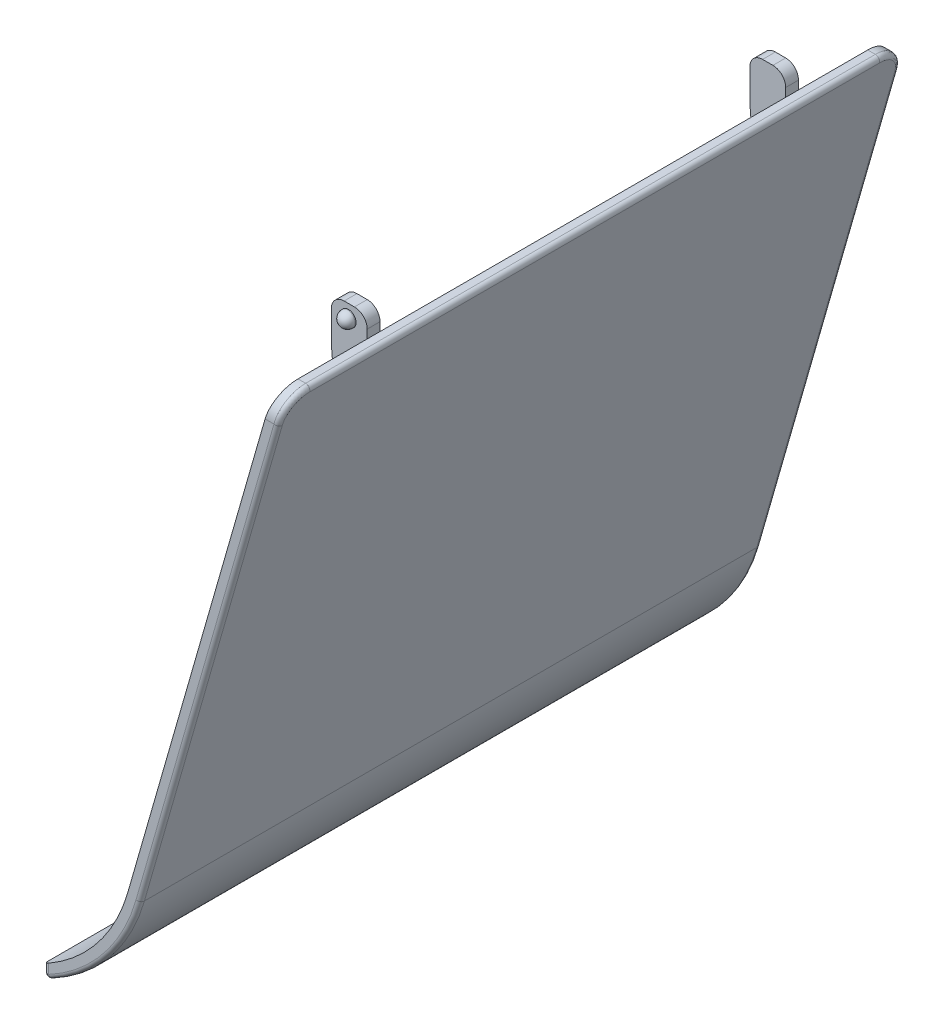
SolidWorks part; units mm, degrees
ref_plane "Front Plane" through (0, 0, 0) normal (0, 0, 1) x (1, 0, 0)
ref_plane "Top Plane" through (0, 0, 0) normal (0, 1, 0) x (1, 0, 0)
ref_plane "Right Plane" through (0, 0, 0) normal (1, 0, 0) x (0, 0, -1)
sketch "Sketch1" plane through (0, 0, 0) normal (0, 0, 1) x (1, 0, 0)
  line L0 (0, 0) -> (-18.2728, 0) construction
  line L1 (0, 0) -> (-16.961, -59.15)
  line L2 (0.3169, 1.105) -> (0, 0) construction
  line L3 (1.4419, -0.4135) -> (-15.5191, -59.5635)
  line L4 (0, 0) -> (1.5604, 0)
  line L5 (-31.0907, -72.9773) -> (-30.7085, -74.4278)
  line L6 (1.7588, 0.6916) -> (1.4419, -0.4135) construction
  line L7 (1.5604, 0) -> (1.4419, -0.4135)
  arc A0 (-30.7085, -74.4278) -> (-15.5191, -59.5635) centre (-36.1862, -53.6373) ccw
  arc A2 (-31.0907, -72.9773) -> (-16.961, -59.15) centre (-36.1862, -53.6373) ccw
  dimension "D6" = 59.15
  dimension "D5" = 20
  dimension "D2" = 72.9773
  dimension "D1" = 74
  dimension "D4" = 1.5
extrude "Boss-Extrude1" add sketch "Sketch1" along normal mid plane 72.85
sketch "Sketch2" plane through (0, 0, 36.425) normal (0, 0, 1) x (1, 0, 0)
  line L0 (-31.0907, -72.9773) -> (-26.794, -72.9773)
  line L1 (-31.0907, -72.9773) -> (-30.7085, -74.4278) construction
  line L2 (-31.0907, -72.9773) -> (-30.7085, -74.4278)
  arc A0 (-31.0907, -72.9773) -> (-16.961, -59.15) centre (-36.1862, -53.6373) ccw construction
  arc A1 (-30.7085, -74.4278) -> (-15.5191, -59.5635) centre (-36.1862, -53.6373) ccw construction
  arc A2 (-30.7085, -74.4278) -> (-26.794, -72.9773) centre (-36.1862, -53.6373) ccw
extrude "Cut-Extrude1" cut sketch "Sketch2" against normal through all
sketch "Sketch3" plane through (0, 0, 36.425) normal (0, 0, 1) x (1, 0, 0)
  line L0 (-26.794, -72.9773) -> (-31.0907, -72.9773) construction
  line L1 (-26.794, -72.9773) -> (-31.0907, -72.9773)
  line L2 (-26.794, -72.9773) -> (-26.794, -71.2947)
  arc A0 (-31.0907, -72.9773) -> (-16.961, -59.15) centre (-36.1862, -53.6373) ccw construction
  arc A1 (-31.0907, -72.9773) -> (-26.794, -71.2947) centre (-36.1862, -53.6373) ccw
extrude "Cut-Extrude2" cut sketch "Sketch3" against normal through all
fillet "Fillet1" radius 3 2 edges at (0.7802, 0, -36.425) (0.7802, 0, 36.425)
sketch "Sketch11" plane through (0, 0, 0) normal (0, 0, 1) x (1, 0, 0)
  line L1 (-2.8942, -10.0932) -> (-4.8167, -9.542)
  line L2 (-0.8602, -3) -> (-16.961, -59.15) construction
  line L3 (-4.8167, -9.542) -> (-3.3283, -4.3512)
  line L5 (-3.3283, -4.3512) -> (-6.2121, -3.5242)
  line L6 (-6.2121, -3.5242) -> (-8.5274, -11.5988)
  line L7 (-8.5274, -11.5988) -> (-3.7211, -12.977)
  line L8 (-3.7211, -12.977) -> (-2.8942, -10.0932)
  dimension "D1" = 3
  dimension "D2" = 10.5
  dimension "D3" = 5
  dimension "D4" = 3
  dimension "D5" = 8.4
sketch "Sketch27" plane through (0, 0, 0) normal (1, 0, 0) x (0, 0, -1)
  line L0 (-33.425, 0) -> (33.425, 0) construction
  line L1 (-23.8, 2.5) -> (-25.3, 2.5)
  line L2 (-23.8, 2.5) -> (-23.8, -2.5)
  line L3 (-23.8, -2.5) -> (-25.3, -2.5)
  line L4 (-25.3, 2.5) -> (-25.3, -2.5)
  line L5 (-33.425, 0) -> (33.425, 0) construction
  dimension "D1" = 2.5
  dimension "D2" = 23.8
  dimension "D3" = 1.5
  dimension "D4" = 2.5
extrude "Boss-Extrude12" add sketch "Sketch27" along normal up to surface (4.9269 mm away) from offset 4.21
sketch "Sketch30" plane through (0, 0, 25.3) normal (0, 0, 1) x (1, 0, 0)
  line L1 (0.7169, 2.5) -> (0, 2.5)
  line L2 (0.7169, 2.5) -> (0.7169, 0)
  line L3 (0.7169, 0) -> (0, 0)
  line L4 (0, 2.5) -> (0, 0)
extrude "Cut-Extrude9" cut sketch "Sketch30" against normal up to next
sketch "Sketch31" plane through (0, 0, 25.3) normal (0, 0, 1) x (1, 0, 0)
  line L0 (0, 2.5) -> (-4.21, 2.5) construction
  line L1 (-4.21, 2.5) -> (-4.21, -2.5) construction
  circle A0 centre (-2.21, 1) radius 0.9
  dimension "D3" = 1.8
  dimension "D1" = 1.5
  dimension "D2" = 2
extrude "Boss-Extrude13" add sketch "Sketch31" along normal blind 1
fillet "Fillet9" radius 1.5 1 edges at (-4.21, 2.5, 24.55)
fillet "Fillet10" radius 1.5 1 edges at (0, 2.5, 24.55)
fillet "Fillet11" radius 0.9 1 edges at (-1.31, 1, 26.3)
mirror "Mirror4" about plane through (0, 0, 0) normal (0, 0, 1) of "Fillet11", "Fillet10", "Fillet9", "Boss-Extrude13", "Cut-Extrude9", "Boss-Extrude12"
fillet "Fillet12" radius 0.5 10 edges at (-19.728, -67.4711, 36.425) (-7.4094, -31.2817, 36.425) (1.3085, -0.8787, 35.5463) (-19.728, -67.4711, -36.425) (-7.4094, -31.2817, -36.425) (1.3085, -0.8787, -35.5463) (-26.794, -72.136, -36.425) (-26.794, -72.136, 36.425) (-26.794, -72.9773, 0) (1.5604, 0, 0)
chamfer "Chamfer1" distance 3.5 distance2 10 2 edges at (-0.7169, -2.5, 24.55) (-0.7169, -2.5, -24.55)
